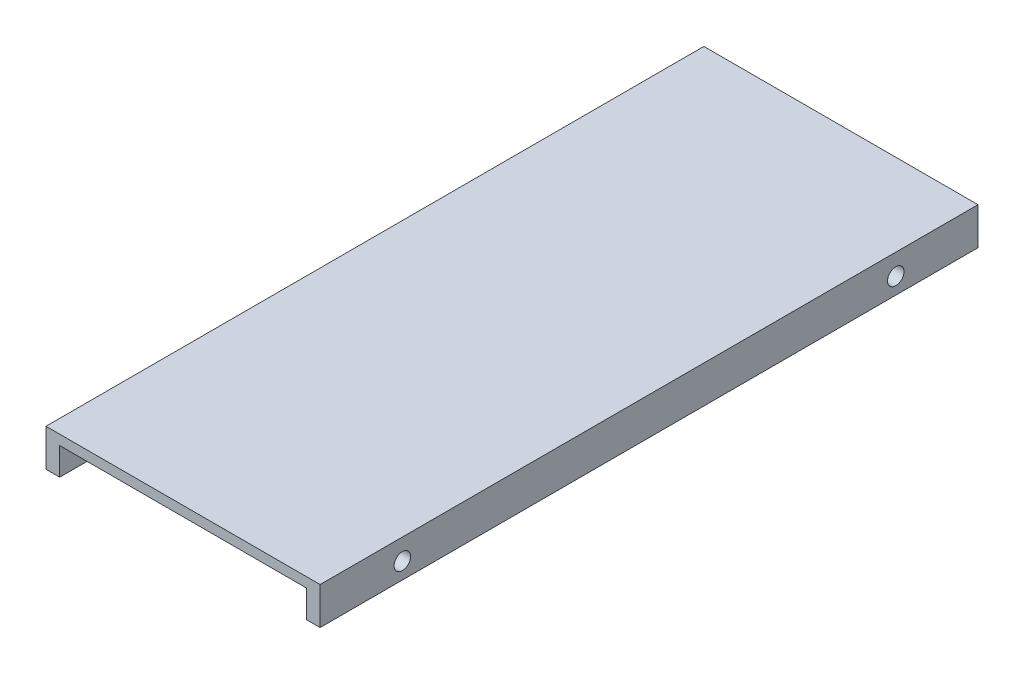
SolidWorks part; units mm, degrees
ref_plane "Front Plane" through (0, 0, 0) normal (0, 0, 1) x (1, 0, 0)
ref_plane "Top Plane" through (0, 0, 0) normal (0, 1, 0) x (1, 0, 0)
ref_plane "Right Plane" through (0, 0, 0) normal (1, 0, 0) x (0, 0, -1)
sketch "Sketch1" plane through (0, 0, 0) normal (0, 0, 1) x (1, 0, 0)
  line L1 (0, 0) -> (25, 0)
  line L2 (0, 0) -> (0, 68)
  line L4 (25, 0) -> (25, 50)
  line L5 (0, 68) -> (500, 68)
  line L7 (25, 50) -> (475, 50)
  line L10 (500, 68) -> (500, 0)
  line L11 (500, 0) -> (475, 0)
  line L12 (475, 50) -> (475, 0)
  dimension "D1" = 25
  dimension "D2" = 68
  dimension "D5" = 25
  dimension "D6" = 68
extrude "Boss-Extrude1" add sketch "Sketch1" along normal blind 1200
sketch "Sketch2" plane through (500, 0, 0) normal (1, 0, 0) x (0, 0, -1)
  line L0 (-1200, 0) -> (0, 0) construction
  line L1 (-1200, 0) -> (-1200, 68) construction
  circle A0 centre (-1050, 30) radius 15
  dimension "D1" = 30
  dimension "D2" = 30
  dimension "D3" = 150
extrude "Cut-Extrude1" cut sketch "Sketch2" against normal blind 1200
sketch "Sketch4" plane through (500, 0, 0) normal (1, 0, 0) x (0, 0, -1)
  line L0 (-1200, 0) -> (0, 0) construction
  line L1 (0, 0) -> (0, 68) construction
  circle A0 centre (-150, 30) radius 15
  dimension "D1" = 30
  dimension "D2" = 30
  dimension "D3" = 150
extrude "Cut-Extrude2" cut sketch "Sketch4" against normal blind 1200
